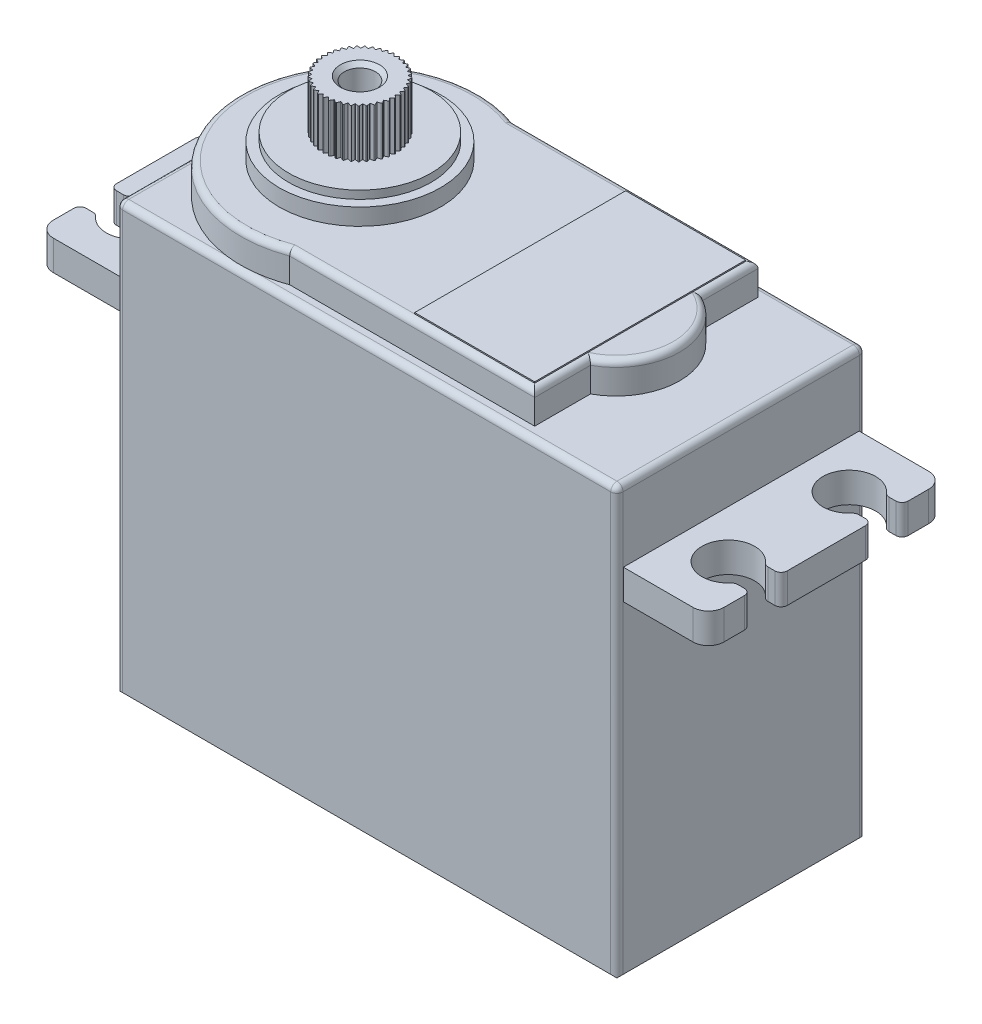
SolidWorks part; units mm, degrees
ref_plane "Front Plane" through (0, 0, 0) normal (0, 0, 1) x (1, 0, 0)
ref_plane "Top Plane" through (0, 0, 0) normal (0, 1, 0) x (1, 0, 0)
ref_plane "Right Plane" through (0, 0, 0) normal (1, 0, 0) x (0, 0, -1)
sketch "Sketch1" plane through (0, 0, 10) normal (0, 1, 0) x (1, 0, 0)
  line L0 (-20.1676, 20.0203) -> (-20.1676, -0.0203)
  line L1 (-20.1676, -0.0203) -> (20.1676, -0.0203)
  line L2 (20.1676, -0.0203) -> (20.1676, 20.0203)
  line L3 (20.1676, 20.0203) -> (-20.1676, 20.0203)
  line L4 (-20.1676, 20.0203) -> (20.1676, -0.0203) construction
  line L5 (20.1676, 20.0203) -> (-20.1676, -0.0203) construction
  point P5 (0, 10)
  dimension "D1" = 20.0406
  dimension "D2" = 40.3352
extrude "Boss-Extrude1" add sketch "Sketch1" against normal mid plane 36.6776
sketch "Sketch2" plane through (0, 18.3388, 8.65) normal (0, -1, 0) x (-1, 0, 0)
  line L0 (-12.5182, -0.35) -> (-12.5182, 17.65)
  line L1 (-12.5182, 17.65) -> (7.2213, 17.65)
  line L2 (7.2213, -0.35) -> (-12.5182, -0.35)
  line L3 (20.1676, 8.65) -> (-20.1676, 8.65) construction
  line L4 (20.1676, 18.6703) -> (20.1676, -1.3703) construction
  line L5 (-20.1676, -1.3703) -> (-20.1676, 18.6703) construction
  arc A0 (7.2213, 17.65) -> (7.2213, -0.35) centre (10.5654, 8.65) cw
  point P15 (20.1666, 8.65)
  dimension "D1" = 19.7395
  dimension "D3" = 9.6012
  dimension "D4" = 0.001
  dimension "D2" = 18
extrude "Boss-Extrude2" add sketch "Sketch2" against normal blind 2.5
sketch "Sketch3" plane through (20.1676, 0, 0) normal (1, 0, 0) x (0, 0, -1)
  line L0 (9.5, 12.573) -> (9.5, 10.16)
  line L1 (9.5, 10.16) -> (-9.5, 10.16)
  line L2 (-9.5, 10.16) -> (-9.5, 12.573)
  line L3 (-9.5, 12.573) -> (9.5, 12.573)
  line L4 (9, 18.3388) -> (-9, 18.3388) construction
  dimension "D1" = 2.413
  dimension "D2" = 19
  dimension "D3" = 5.7658
extrude "Boss-Extrude3" add sketch "Sketch3" along normal blind 6.858
sketch "Sketch4" plane through (0, 10.16, 0) normal (0, -1, 0) x (1, 0, 0)
  line L0 (27.0256, 3.65) -> (27.0256, 6.1)
  line L1 (27.0256, 6.1) -> (25.737, 6.1)
  line L2 (25.737, 3.65) -> (27.0256, 3.65)
  line L5 (27.0256, 9.5) -> (27.0256, -9.5) construction
  arc A0 (25.737, 6.1) -> (25.737, 3.65) centre (24.0006, 4.875) ccw
  dimension "D3" = 2.125
  dimension "D1" = 1.2886
  dimension "D2" = 2.45
extrude "Cut-Extrude1" cut sketch "Sketch4" against normal through all
sketch "Sketch5" plane through (0, 10.16, 0) normal (0, -1, 0) x (1, 0, 0)
  line L0 (27.0256, -6.1) -> (27.0256, -3.65)
  line L1 (27.0256, -3.65) -> (25.737, -3.65)
  line L2 (25.737, -6.1) -> (27.0256, -6.1)
  line L3 (27.0256, 3.65) -> (27.0256, -9.5) construction
  arc A0 (25.737, -3.65) -> (25.737, -6.1) centre (24.0006, -4.875) ccw
  dimension "D3" = 2.125
  dimension "D1" = 1.2886
  dimension "D2" = 2.45
extrude "Cut-Extrude2" cut sketch "Sketch5" against normal through all
sketch "Sketch6" plane through (-20.1676, 0, 0) normal (-1, 0, 0) x (0, 0, 1)
  line L0 (-9.5, 10.16) -> (-9.5, 12.573)
  line L1 (-9.5, 12.573) -> (9.5, 12.573)
  line L2 (9.5, 12.573) -> (9.5, 10.16)
  line L3 (9.5, 10.16) -> (-9.5, 10.16)
  line L4 (-10.0203, 18.3388) -> (10.0203, 18.3388) construction
  dimension "D1" = 2.413
  dimension "D2" = 19
  dimension "D3" = 5.7658
extrude "Boss-Extrude4" add sketch "Sketch6" along normal blind 6.858
sketch "Sketch7" plane through (0, 10.16, 0) normal (0, -1, 0) x (1, 0, 0)
  line L0 (-27.0256, -6.1) -> (-25.737, -6.1)
  line L1 (-25.737, -3.65) -> (-27.0256, -3.65)
  line L2 (-27.0256, -3.65) -> (-27.0256, -6.1)
  line L3 (-27.0256, -9.5) -> (-27.0256, 9.5) construction
  arc A0 (-25.737, -6.1) -> (-25.737, -3.65) centre (-24.0006, -4.875) ccw
  dimension "D3" = 2.125
  dimension "D1" = 1.2886
  dimension "D2" = 2.45
extrude "Cut-Extrude3" cut sketch "Sketch7" against normal through all
sketch "Sketch8" plane through (0, 10.16, 0) normal (0, -1, 0) x (1, 0, 0)
  line L0 (-27.0256, 3.65) -> (-25.737, 3.65)
  line L1 (-25.737, 6.1) -> (-27.0256, 6.1)
  line L2 (-27.0256, 6.1) -> (-27.0256, 3.65)
  line L3 (-27.0256, -3.65) -> (-27.0256, 9.5) construction
  arc A0 (-25.737, 3.65) -> (-25.737, 6.1) centre (-24.0006, 4.875) ccw
  dimension "D2" = 2.125
  dimension "D1" = 1.2886
  dimension "D3" = 2.45
extrude "Cut-Extrude4" cut sketch "Sketch8" against normal through all
sketch "Sketch9" plane through (0, 18.3388, 8.65) normal (0, -1, 0) x (-1, 0, 0)
  line L0 (-12.5182, 13.15) -> (-12.5182, 4.15)
  line L3 (-12.5182, 17.65) -> (-12.5182, -0.35) construction
  arc A0 (-12.5182, 4.15) -> (-12.5182, 13.15) centre (-10.082, 8.65) cw
  point P3 (-12.5182, 8.65)
  dimension "D1" = 5.1171
  dimension "D2" = 9
extrude "Boss-Extrude5" add sketch "Sketch9" against normal blind 2.5
sketch "Sketch10" plane through (0, 20.8388, 0) normal (0, 1, 0) x (-1, 0, 0)
  circle A0 centre (10.5654, 0) radius 6.5
  dimension "D1" = 13
extrude "Boss-Extrude6" add sketch "Sketch10" along normal blind 1.35
sketch "Sketch11" plane through (0, 22.1888, 0) normal (0, 1, 0) x (-1, 0, 0)
  circle A0 centre (10.5654, 0) radius 5.75
extrude "Boss-Extrude7" add sketch "Sketch11" along normal blind 0.65
sketch "Sketch12" plane through (0, 22.8388, 0) normal (0, 1, 0) x (-1, 0, 0)
  line B0 (9.3322, -2.458) -> (9.0287, -2.5765)
  line B1 (9.0287, -2.5765) -> (8.9887, -2.2531)
  line B2 (8.9715, -2.241) -> (8.6534, -2.3117)
  line B3 (8.6534, -2.3117) -> (8.6632, -1.986)
  line B4 (8.6481, -1.9714) -> (8.3229, -1.9928)
  line B5 (8.3229, -1.9928) -> (8.3824, -1.6724)
  line B6 (8.3696, -1.6556) -> (8.045, -1.6271)
  line B7 (8.045, -1.6271) -> (8.1527, -1.3195)
  line B8 (8.1426, -1.301) -> (7.8261, -1.2233)
  line B9 (7.8261, -1.2233) -> (7.9795, -0.9358)
  line B10 (7.9724, -0.9159) -> (7.6715, -0.7908)
  line B11 (7.6715, -0.7908) -> (7.867, -0.5301)
  line B12 (7.863, -0.5094) -> (7.5847, -0.3398)
  line B13 (7.5847, -0.3398) -> (7.8177, -0.112)
  line B14 (7.8169, -0.0909) -> (7.5678, 0.1192)
  line B15 (7.5678, 0.1192) -> (7.8328, 0.3088)
  line B16 (7.8352, 0.3297) -> (7.6211, 0.5754)
  line B17 (7.6211, 0.5754) -> (7.912, 0.7223)
  line B18 (7.9176, 0.7426) -> (7.7434, 1.0181)
  line B19 (7.7434, 1.0181) -> (8.0533, 1.1189)
  line B20 (8.062, 1.1381) -> (7.9319, 1.4369)
  line B21 (7.9319, 1.4369) -> (8.2536, 1.4892)
  line B22 (8.265, 1.5069) -> (8.1821, 1.8221)
  line B23 (8.1821, 1.8221) -> (8.508, 1.8247)
  line B24 (8.522, 1.8404) -> (8.4882, 2.1645)
  line B25 (8.4882, 2.1645) -> (8.8106, 2.1174)
  line B26 (8.8269, 2.1308) -> (8.8429, 2.4562)
  line B27 (8.8429, 2.4562) -> (9.1544, 2.3604)
  line B28 (9.1725, 2.3712) -> (9.2381, 2.6904)
  line B29 (9.2381, 2.6904) -> (9.5313, 2.5481)
  line B30 (9.5508, 2.556) -> (9.6643, 2.8615)
  line B31 (9.6643, 2.8615) -> (9.9324, 2.6761)
  line B32 (9.9529, 2.6809) -> (10.1117, 2.9655)
  line B33 (10.1117, 2.9655) -> (10.3483, 2.7414)
  line B34 (10.3693, 2.743) -> (10.5697, 3)
  line B35 (10.5697, 3) -> (10.7693, 2.7424)
  line B36 (10.7903, 2.7408) -> (11.0276, 2.9642)
  line B37 (11.0276, 2.9642) -> (11.1855, 2.6792)
  line B38 (11.2061, 2.6743) -> (11.4746, 2.8589)
  line B39 (11.4746, 2.8589) -> (11.5873, 2.5531)
  line B40 (11.6068, 2.5452) -> (11.9004, 2.6866)
  line B41 (11.9004, 2.6866) -> (11.965, 2.3672)
  line B42 (11.9831, 2.3564) -> (12.2948, 2.4513)
  line B43 (12.2948, 2.4513) -> (12.31, 2.1258)
  line B44 (12.3262, 2.1124) -> (12.6488, 2.1586)
  line B45 (12.6488, 2.1586) -> (12.614, 1.8346)
  line B46 (12.628, 1.8188) -> (12.9539, 1.8153)
  line B47 (12.9539, 1.8153) -> (12.87, 1.5004)
  line B48 (12.8815, 1.4827) -> (13.203, 1.4294)
  line B49 (13.203, 1.4294) -> (13.0721, 1.131)
  line B50 (13.0807, 1.1117) -> (13.3903, 1.01)
  line B51 (13.3903, 1.01) -> (13.2153, 0.7351)
  line B52 (13.2209, 0.7147) -> (13.5113, 0.567)
  line B53 (13.5113, 0.567) -> (13.2965, 0.322)
  line B54 (13.2989, 0.301) -> (13.5634, 0.1106)
  line B55 (13.5634, 0.1106) -> (13.3136, -0.0987)
  line B56 (13.3128, -0.1198) -> (13.5451, -0.3483)
  line B57 (13.5451, -0.3483) -> (13.2664, -0.5171)
  line B58 (13.2623, -0.5378) -> (13.457, -0.7991)
  line B59 (13.457, -0.7991) -> (13.1558, -0.9233)
  line B60 (13.1486, -0.9431) -> (13.3012, -1.2311)
  line B61 (13.3012, -1.2311) -> (12.9845, -1.3079)
  line B62 (12.9744, -1.3264) -> (13.0812, -1.6343)
  line B63 (13.0812, -1.6343) -> (12.7565, -1.6618)
  line B64 (12.7437, -1.6786) -> (12.8022, -1.9992)
  line B65 (12.8022, -1.9992) -> (12.4771, -1.9768)
  line B66 (12.4619, -1.9914) -> (12.4708, -2.3172)
  line B67 (12.4708, -2.3172) -> (12.1529, -2.2455)
  line B68 (12.1357, -2.2576) -> (12.0948, -2.5809)
  line B69 (12.0948, -2.5809) -> (11.7916, -2.4615)
  line B70 (11.7727, -2.4708) -> (11.6829, -2.7841)
  line B71 (11.6829, -2.7841) -> (11.4014, -2.6198)
  line B72 (11.3813, -2.6262) -> (11.2448, -2.9221)
  line B73 (11.2448, -2.9221) -> (10.9917, -2.7168)
  line B74 (10.9709, -2.7199) -> (10.7908, -2.9915)
  line B75 (10.7908, -2.9915) -> (10.572, -2.75)
  line B76 (10.5509, -2.75) -> (10.3315, -2.9909)
  line B77 (10.3315, -2.9909) -> (10.1522, -2.7188)
  line B78 (10.1313, -2.7155) -> (9.8777, -2.9201)
  line B79 (9.8777, -2.9201) -> (9.742, -2.6238)
  line B80 (9.7219, -2.6174) -> (9.44, -2.7809)
  line B81 (9.44, -2.7809) -> (9.3511, -2.4674)
  arc B82 (9.3511, -2.4674) -> (9.3322, -2.458) centre (10.5654, 0) cw
  arc B83 (8.9887, -2.2531) -> (8.9715, -2.241) centre (10.5654, 0) cw
  arc B84 (8.6632, -1.986) -> (8.6481, -1.9714) centre (10.5654, 0) cw
  arc B85 (8.3824, -1.6724) -> (8.3696, -1.6556) centre (10.5654, 0) cw
  arc B86 (8.1527, -1.3195) -> (8.1426, -1.301) centre (10.5654, 0) cw
  arc B87 (7.9795, -0.9358) -> (7.9724, -0.9159) centre (10.5654, 0) cw
  arc B88 (7.867, -0.5301) -> (7.863, -0.5094) centre (10.5654, 0) cw
  arc B89 (7.8177, -0.112) -> (7.8169, -0.0909) centre (10.5654, 0) cw
  arc B90 (7.8328, 0.3088) -> (7.8352, 0.3297) centre (10.5654, 0) cw
  arc B91 (7.912, 0.7223) -> (7.9176, 0.7426) centre (10.5654, 0) cw
  arc B92 (8.0533, 1.1189) -> (8.062, 1.1381) centre (10.5654, 0) cw
  arc B93 (8.2536, 1.4892) -> (8.265, 1.5069) centre (10.5654, 0) cw
  arc B94 (8.508, 1.8247) -> (8.522, 1.8404) centre (10.5654, 0) cw
  arc B95 (8.8106, 2.1174) -> (8.8269, 2.1308) centre (10.5654, 0) cw
  arc B96 (9.1544, 2.3604) -> (9.1725, 2.3712) centre (10.5654, 0) cw
  arc B97 (9.5313, 2.5481) -> (9.5508, 2.556) centre (10.5654, 0) cw
  arc B98 (9.9324, 2.6761) -> (9.9529, 2.6809) centre (10.5654, 0) cw
  arc B99 (10.3483, 2.7414) -> (10.3693, 2.743) centre (10.5654, 0) cw
  arc B100 (10.7693, 2.7424) -> (10.7903, 2.7408) centre (10.5654, 0) cw
  arc B101 (11.1855, 2.6792) -> (11.2061, 2.6743) centre (10.5654, 0) cw
  arc B102 (11.5873, 2.5531) -> (11.6068, 2.5452) centre (10.5654, 0) cw
  arc B103 (11.965, 2.3672) -> (11.9831, 2.3564) centre (10.5654, 0) cw
  arc B104 (12.31, 2.1258) -> (12.3262, 2.1124) centre (10.5654, 0) cw
  arc B105 (12.614, 1.8346) -> (12.628, 1.8188) centre (10.5654, 0) cw
  arc B106 (12.87, 1.5004) -> (12.8815, 1.4827) centre (10.5654, 0) cw
  arc B107 (13.0721, 1.131) -> (13.0807, 1.1117) centre (10.5654, 0) cw
  arc B108 (13.2153, 0.7351) -> (13.2209, 0.7147) centre (10.5654, 0) cw
  arc B109 (13.2965, 0.322) -> (13.2989, 0.301) centre (10.5654, 0) cw
  arc B110 (13.3136, -0.0987) -> (13.3128, -0.1198) centre (10.5654, 0) cw
  arc B111 (13.2664, -0.5171) -> (13.2623, -0.5378) centre (10.5654, 0) cw
  arc B112 (13.1558, -0.9233) -> (13.1486, -0.9431) centre (10.5654, 0) cw
  arc B113 (12.9845, -1.3079) -> (12.9744, -1.3264) centre (10.5654, 0) cw
  arc B114 (12.7565, -1.6618) -> (12.7437, -1.6786) centre (10.5654, 0) cw
  arc B115 (12.4771, -1.9768) -> (12.4619, -1.9914) centre (10.5654, 0) cw
  arc B116 (12.1529, -2.2455) -> (12.1357, -2.2576) centre (10.5654, 0) cw
  arc B117 (11.7916, -2.4615) -> (11.7727, -2.4708) centre (10.5654, 0) cw
  arc B118 (11.4014, -2.6198) -> (11.3813, -2.6262) centre (10.5654, 0) cw
  arc B119 (10.9917, -2.7168) -> (10.9709, -2.7199) centre (10.5654, 0) cw
  arc B120 (10.572, -2.75) -> (10.5509, -2.75) centre (10.5654, 0) cw
  arc B121 (10.1522, -2.7188) -> (10.1313, -2.7155) centre (10.5654, 0) cw
  arc B122 (9.742, -2.6238) -> (9.7219, -2.6174) centre (10.5654, 0) cw
sketch_block_instance "Block1-1"
sketch_block "Block1"
extrude "Boss-Extrude8" add sketch "Sketch12" along normal blind 3.9
sketch "Sketch13" plane through (-20.1676, 0, 0) normal (-1, 0, 0) x (0, 0, 1)
  line L0 (-3.375, -11.4112) -> (3.375, -11.4112)
  line L1 (3.375, -11.4112) -> (3.375, -15.4112)
  line L2 (3.375, -15.4112) -> (-3.375, -15.4112)
  line L3 (-3.375, -15.4112) -> (-3.375, -11.4112)
  line L4 (9.6012, 18.3388) -> (-9.6012, 18.3388) construction
  dimension "D1" = 4
  dimension "D2" = 6.75
  dimension "D3" = 29.75
extrude "Boss-Extrude9" add sketch "Sketch13" along normal blind 5 draft 5
ref_plane "Plane2" through (0, 0, 4.875) normal (0, 0, 1) x (1, 0, 0)
ref_plane "Plane3" through (0, 0, -4.875) normal (0, 0, 1) x (1, 0, 0)
hole_wizard "Ø2.5 (2.5) Diameter Hole1" positions "Sketch19" profile "Sketch18" hole size "Ø2.5" standard "ANSI Metric"
sketch "Sketch19" plane through (0, 26.7388, 0) normal (0, 1, 0) x (1, 0, 0)
  point P9 (-10.5654, 0)
sketch "Sketch18" plane through (-10.5654, 26.7388, 0) normal (1, 0, 0) x (0, 0, 1)
  line L0 (0, 0) -> (0, 9.2511)
  line L1 (0, 9.2511) -> (1.25, 8.5)
  line L2 (1.25, 8.5) -> (1.25, 0)
  line L5 (1.25, 0) -> (0, 0)
  line L10 (0, 9.2511) -> (-1.25, 8.5) construction
  line L11 (0, -6.35) -> (0, 107.95) construction
  dimension "Hole Dia." = 2.5
  dimension "Hole Depth" = 8.5
  dimension "Drill Angle" = 118
fillet "Fillet1" radius 0.055 41 edges at (-7.5847, 24.7888, -0.3398) (-11.6829, 24.7888, -2.7841) (-9.8777, 24.7888, -2.9201) (-7.6211, 24.7888, 0.5754) (-12.4708, 24.7888, -2.3172) (-10.7908, 24.7888, -2.9915) (-7.7434, 24.7888, 1.0181) (-7.5678, 24.7888, 0.1192) (-7.6715, 24.7888, -0.7908) (-11.0276, 24.7888, 2.9642) (-12.0948, 24.7888, -2.5809) (-11.4746, 24.7888, 2.8589) (-11.2448, 24.7888, -2.9221) (-10.5697, 24.7888, 3) (-10.3315, 24.7888, -2.9909) (-11.9004, 24.7888, 2.6866) (-10.1117, 24.7888, 2.9655) (-13.5451, 24.7888, -0.3483) (-12.2948, 24.7888, 2.4513) (-13.457, 24.7888, -0.7991) (-9.6643, 24.7888, 2.8615) (-13.3012, 24.7888, -1.2311) (-12.6488, 24.7888, 2.1586) (-13.0812, 24.7888, -1.6343) (-9.2381, 24.7888, 2.6904) (-12.8022, 24.7888, -1.9992) (-12.9539, 24.7888, 1.8153) (-7.8261, 24.7888, -1.2233) (-8.8429, 24.7888, 2.4562) (-8.045, 24.7888, -1.6271) (-13.203, 24.7888, 1.4294) (-8.3229, 24.7888, -1.9928) (-8.4882, 24.7888, 2.1645) (-8.6534, 24.7888, -2.3117) (-13.3903, 24.7888, 1.01) (-9.0287, 24.7888, -2.5765) (-8.1821, 24.7888, 1.8221) (-13.5113, 24.7888, 0.567) (-7.9319, 24.7888, 1.4369) (-9.44, 24.7888, -2.7809) (-13.5634, 24.7888, 0.1106) tangent propagation no
chamfer "Chamfer1" distance 2.5 angle 45 4 edges at (0, -18.3388, 10.0203) (-20.1676, -18.3388, 0) (0, -18.3388, -10.0203) (20.1676, -18.3388, 0)
chamfer "Chamfer2" distance 0.325 angle 45 1 edges at (-10.5654, 26.7388, 1.25)
fillet "Fillet2" radius 0.5 30 edges at (25.737, 11.3665, 3.65) (27.0256, 11.3665, 3.65) (20.1676, 18.3388, 0) (20.1676, 1.25, -10.0203) (0, 18.3388, -10.0203) (-27.0256, 11.3665, -6.1) (25.737, 11.3665, -6.1) (-25.737, 11.3665, -6.1) (-25.737, 11.3665, -3.65) (-20.1676, 18.3388, 0) (-20.1676, 1.25, -10.0203) (-27.0256, 11.3665, -3.65) (-27.0256, 11.3665, 3.65) (-25.737, 11.3665, 3.65) (27.0256, 11.3665, -3.65) (-25.737, 11.3665, 6.1) (-27.0256, 11.3665, 6.1) (15.1991, 20.8388, 0) (12.5182, 20.8388, 6.75) (12.5182, 20.8388, -6.75) (2.6484, 20.8388, 9) (2.6484, 20.8388, -9) (-20.1666, 20.8388, 0) (27.0256, 11.3665, -6.1) (25.737, 11.3665, 6.1) (25.737, 11.3665, -3.65) (27.0256, 11.3665, 6.1) (0, 18.3388, 10.0203) (20.1676, 1.25, 10.0203) (-20.1676, 1.25, 10.0203) tangent propagation no
fillet "Fillet3" radius 1.25 8 edges at (-22.6676, -11.6299, 3.1563) (27.0256, 11.3665, -9.5) (-27.0256, 11.3665, 9.5) (27.0256, 11.3665, 9.5) (-27.0256, 11.3665, -9.5) (-22.6676, -11.6299, -3.1563) (-22.6676, -15.1925, 3.1563) (-22.6676, -15.1925, -3.1563) tangent propagation no
sketch "Sketch20" plane through (0, 20.8388, 0) normal (0, 1, 0) x (1, 0, 0)
  line L0 (-7.3124, -8.5) -> (12.0182, -8.5) construction
  line L1 (12.0182, 8.5) -> (2.3529, 8.5)
  line L2 (12.0182, 8.5) -> (12.0182, -8.5)
  line L3 (12.0182, -8.5) -> (2.3529, -8.5)
  line L4 (2.3529, 8.5) -> (2.3529, -8.5)
extrude "Boss-Extrude10" add sketch "Sketch20" along normal blind 0.1
